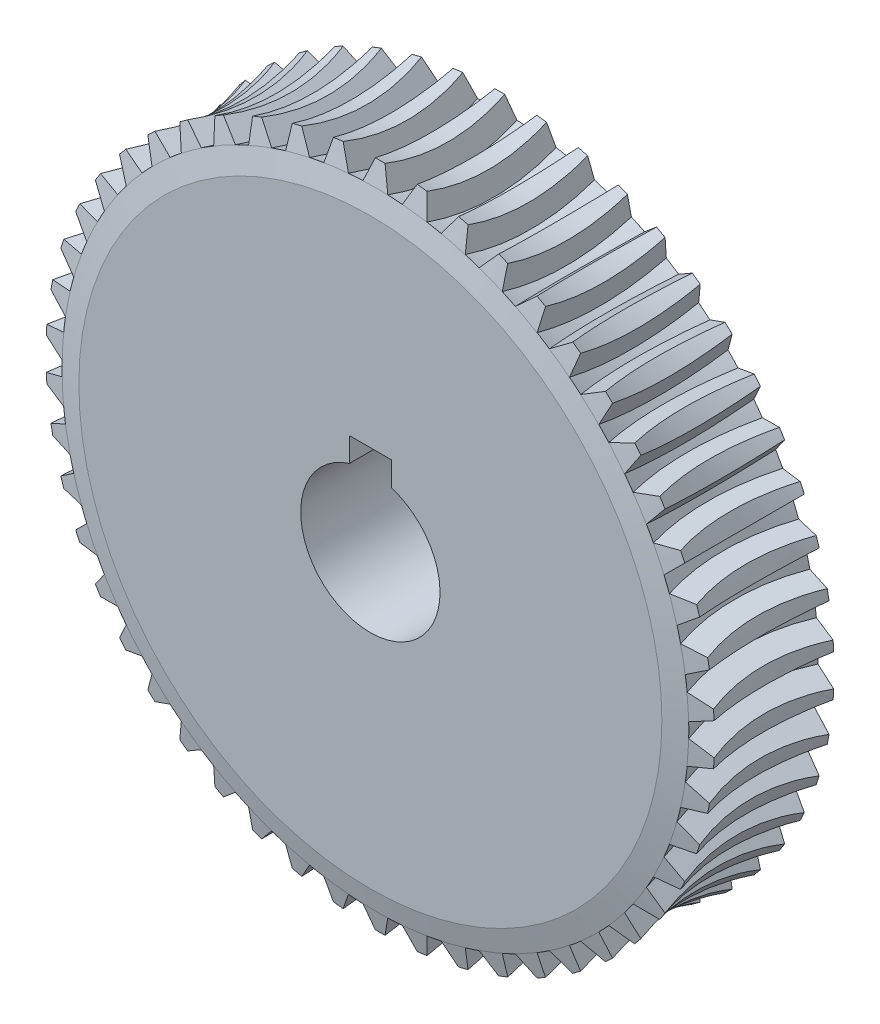
SolidWorks part; units mm, degrees
material "Phosphor bronze 10% D, UNS C52400"
ref_plane "Front Plane" through (0, 0, 0) normal (0, 0, 1) x (1, 0, 0)
ref_plane "Top Plane" through (0, 0, 0) normal (0, 1, 0) x (1, 0, 0)
ref_plane "Right Plane" through (0, 0, 0) normal (1, 0, 0) x (0, 0, -1)
sketch "Sketch1" plane through (0, 0, 0) normal (0, 0, 1) x (1, 0, 0)
  circle A0 centre (0, 0) radius 22.5
  dimension "D1" = 45
extrude "Boss-Extrude1" add sketch "Sketch1" along normal blind 10
sketch "Sketch2" plane through (0, 0, 0) normal (0, 1, 0) x (1, 0, 0)
  line L1 (-22.5, -10) -> (-22.5, -9.64)
  line L2 (0, -10) -> (0, 4.1494)
  line L3 (-22.5, 0) -> (-22.5, -10) construction
  line L4 (-20.93, -10) -> (-22.5, -9.64)
  line L5 (-20.93, -10) -> (-22.5, -10)
  line L6 (22.5, 0) -> (-22.5, 0) construction
  line L8 (-20.93, 0) -> (-22.5, 0)
  line L9 (-20.93, 0) -> (-22.5, -0.36)
  line L10 (-22.5, 0) -> (-22.5, -0.36)
  dimension "D2" = 0.36
revolve "Cut-Revolve1" cut sketch "Sketch2" angle 360 about L2 region at (-21.9767, 0, 9.88) region at (-21.9767, 0, 0.12)
sketch "Sketch3" plane through (0, 0, 0) normal (0, 1, 0) x (1, 0, 0)
  line L0 (-22.5, -0.36) -> (-22.5, -9.64)
  line L1 (0, 0) -> (0, -16.1614)
  arc A0 (-22.5, -0.36) -> (-22.5, -9.64) centre (-38.2514, -5) cw
revolve "Cut-Revolve2" cut sketch "Sketch3" angle 360 about L1 region at (-22.2318, 0, 5)
ref_plane "Plane1" through (0, 0, 0.36) normal (0, 0, -1) x (-1, 0, 0)
sketch "Sketch4" plane through (0, 0, 0.36) normal (0, 0, -1) x (-1, 0, 0)
  line L0 (-0.89, 22.4824) -> (-1.2376, 21.5054)
  line L1 (0.35, 24) -> (-0.35, 24)
  line L2 (0.89, 21.5054) -> (-0.89, 21.5054)
  line L5 (0, -22.5) -> (0, -24)
  line L6 (0.35, 24) -> (0.89, 22.4824)
  line L7 (-0.35, 24) -> (-0.89, 22.4824)
  line L8 (0.89, 22.4824) -> (1.2376, 21.5054)
  line L9 (-0.89, 21.5054) -> (-1.2376, 21.5054)
  line L10 (0.89, 21.5054) -> (1.2376, 21.5054)
  dimension "D2" = 0.7
  dimension "D3" = 1.78
extrude "Boss-Extrude2" add sketch "Sketch4" against normal blind 9.28 contours L1 L7 L2 L6 region at (0, 22.5202, 0.36)
pattern_circular "CirPattern1" count 50 every 7.2 about axis through (0, 0, 0.36) along (0, 0, -1) of "Boss-Extrude2"
sketch "Sketch5" plane through (0, 0, 0) normal (1, 0, 0) x (0, 0, -1)
  line L0 (-0.36, 22.4892) -> (-1.1657, 26.003)
  line L1 (-0.36, -23.023) -> (-0.36, 23.023) construction
  line L2 (-1.1657, 26.003) -> (-0.36, 26.003)
  line L3 (-0.36, 22.4892) -> (-0.36, 26.003)
  line L4 (0, 0) -> (-16.1048, 0)
  line L6 (-9.64, 22.4892) -> (-9.64, 26.003)
  line L7 (-8.8343, 26.003) -> (-9.64, 26.003)
  line L8 (-9.64, 22.4892) -> (-8.8343, 26.003)
revolve "Cut-Revolve3" cut sketch "Sketch5" angle 360 about L4 region at (0, 24.8317, 0.6286) region at (0, 24.8317, 9.3714)
sketch "Sketch6" plane through (0, 0, 0) normal (1, 0, 0) x (0, 0, -1)
  line L1 (-10, 0) -> (13.4271, 0)
  line L2 (-10, 20.93) -> (-10, -20.93) construction
  line L3 (-0.707, 24) -> (-0.707, 27.3429)
  line L4 (-9.293, 24) -> (-9.293, 27.3429)
  line L5 (-9.293, 27.3429) -> (-0.707, 27.3429)
  arc A0 (-0.707, 24) -> (-9.293, 24) centre (-5, 37.2135) cw
revolve "Cut-Revolve7" cut sketch "Sketch6" angle 360 about L1 region at (0, 25.4383, 5)
sketch "Sketch7" plane through (0, 0, 0) normal (0, 0, -1) x (-1, 0, 0)
  circle A0 centre (0, 0) radius 11.5
  dimension "D1" = 23
extrude "Boss-Extrude3" add sketch "Sketch7" along normal blind 6.8
sketch "Sketch8" plane through (0, 0, -6.8) normal (0, 0, -1) x (-1, 0, 0)
  circle A0 centre (0, 0) radius 5
  dimension "D1" = 10
extrude "Cut-Extrude1" cut sketch "Sketch8" against normal through all both and the other way through all
sketch "Sketch9" plane through (0, 0, -6.8) normal (0, 0, -1) x (-1, 0, 0)
  line L2 (-1.5, 1.7279) -> (1.5, 1.7279)
  line L3 (-1.5, 1.7279) -> (-1.5, 6.5)
  line L4 (-1.5, 6.5) -> (1.5, 6.5)
  line L5 (1.5, 1.7279) -> (1.5, 6.5)
  line L6 (-1.5, 1.7279) -> (1.5, 6.5) construction
  line L7 (-1.5, 6.5) -> (1.5, 1.7279) construction
  point P5 (0, 4.1139)
  dimension "D2" = 3
extrude "Cut-Extrude2" cut sketch "Sketch9" against normal through all both and the other way through all
